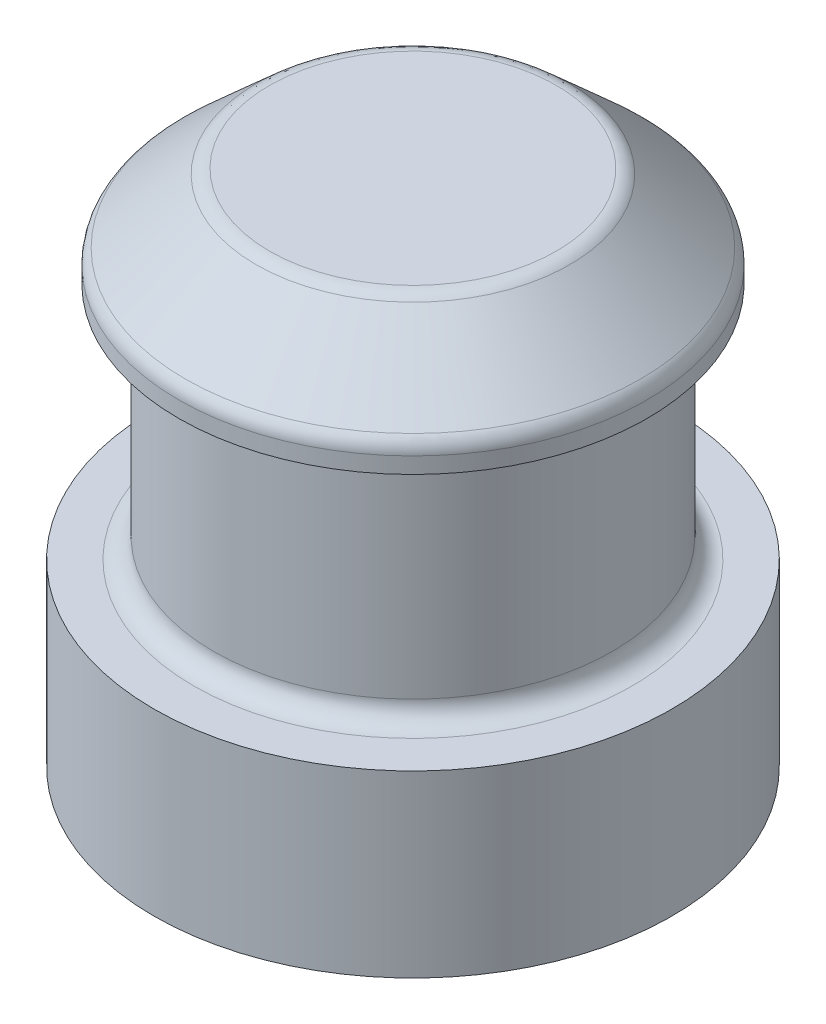
SolidWorks part; units mm, degrees
ref_plane "Front Plane" through (0, 0, 0) normal (0, 0, 1) x (1, 0, 0)
ref_plane "Top Plane" through (0, 0, 0) normal (0, 1, 0) x (1, 0, 0)
ref_plane "Right Plane" through (0, 0, 0) normal (1, 0, 0) x (0, 0, -1)
sketch "Sketch1" plane through (0, 0, 0) normal (0, 1, 0) x (1, 0, 0)
  line L5 (7, -7) -> (-7, 7) construction
  line L6 (7, 7) -> (-7, -7) construction
  circle A0 centre (0, 0) radius 2.6
  point P0 (0, 0)
  dimension "D3" = 5.2
  dimension "D1" = 14
  dimension "D2" = 14
extrude "Boss-Extrude1" add sketch "Sketch1" along normal blind 1.8
ref_plane "Plane1" through (0, 1.8, 0) normal (0, 1, 0) x (1, 0, 0)
sketch "Sketch2" plane through (0, 1.8, 0) normal (0, 1, 0) x (1, 0, 0)
  circle A0 centre (0, 0) radius 2
extrude "Boss-Extrude2" add sketch "Sketch2" along normal blind 2.4
ref_plane "Plane2" through (0, 4.2, 0) normal (0, 1, 0) x (1, 0, 0)
sketch "Sketch3" plane through (0, 4.2, 0) normal (0, 1, 0) x (1, 0, 0)
  circle A0 centre (0, 0) radius 2.35
  circle A1 centre (0, 0) radius 2 construction
extrude "Boss-Extrude3" add sketch "Sketch3" along normal blind 1
chamfer "Chamfer1" distance 0.75 angle 48 1 edges at (0, 5.2, 2.35) first distance on face at (0, 5.2, 2.35)
fillet "Fillet1" radius 0.2 3 edges at (0, 5.2, 1.517) (0, 4.45, 2.35) (0, 1.8, 2)
scale "Scale1" scale about centroid uniform scaling yes scale factor 1.15
